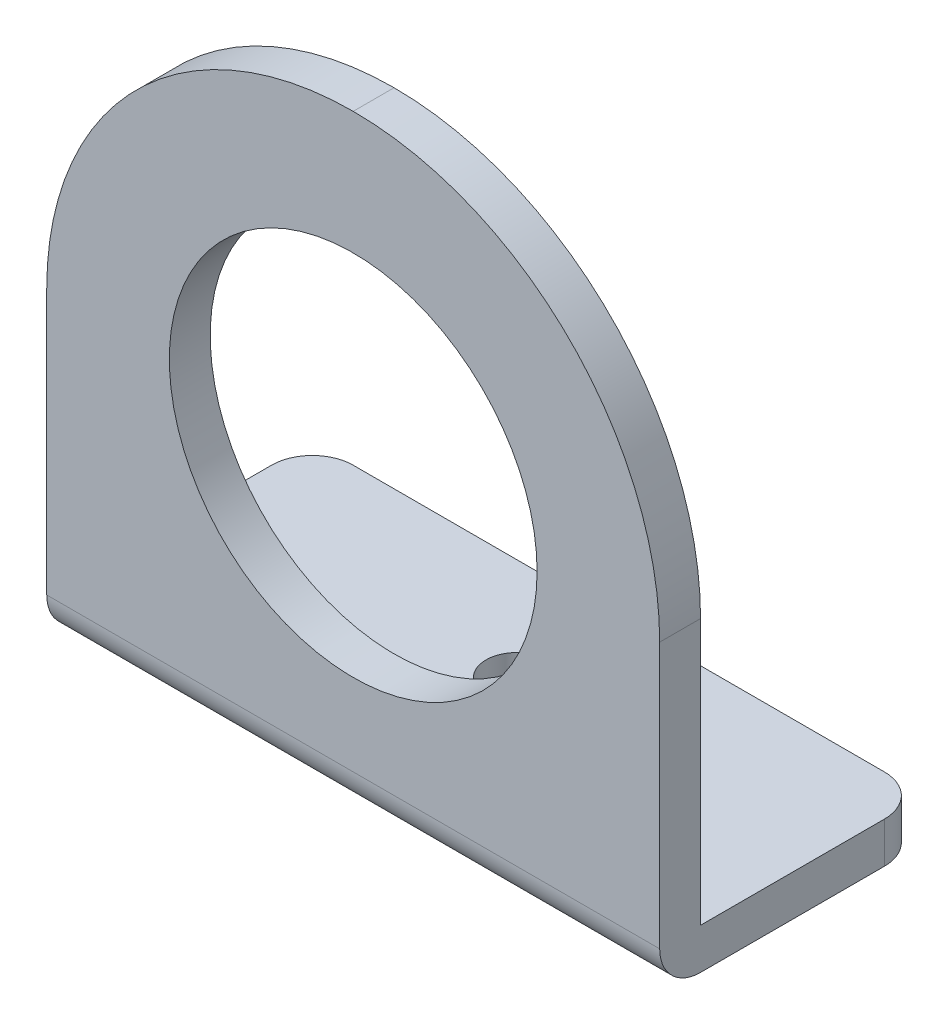
SolidWorks part; units mm, degrees
ref_plane "Front Plane" through (0, 0, 0) normal (0, 0, 1) x (1, 0, 0)
ref_plane "Top Plane" through (0, 0, 0) normal (0, 1, 0) x (1, 0, 0)
ref_plane "Right Plane" through (0, 0, 0) normal (1, 0, 0) x (0, 0, -1)
sketch "Sketch1" plane through (0, 0, 0) normal (0, 0, 1) x (1, 0, 0)
  line L1 (15, 15) -> (-15, 15)
  line L2 (15, 15) -> (15, -15)
  line L3 (15, -15) -> (-15, -15)
  line L4 (-15, 15) -> (-15, -15)
  line L5 (15, 15) -> (-15, -15) construction
  line L6 (15, -15) -> (-15, 15) construction
  point P0 (0, 0)
  dimension "D1" = 30
  dimension "D2" = 30
extrude "Boss-Extrude1" add sketch "Sketch1" along normal blind 2
sketch "Sketch2" plane through (0, 0, 2) normal (0, 0, 1) x (1, 0, 0)
  circle A0 centre (0, 0) radius 9
  dimension "D1" = 18
extrude "Cut-Extrude1" cut sketch "Sketch2" against normal through all contours A0
fillet "Fillet1" radius 15 2 edges at (-15, 15, 1) (15, 15, 1)
sketch "Sketch3" plane through (0, 0, 0) normal (0, 0, -1) x (-1, 0, 0)
  line L0 (15, 0) -> (15, -15) construction
  line L1 (-15, -15) -> (15, -15)
  line L2 (-15, -15) -> (-15, -13)
  line L3 (-15, -13) -> (15, -13)
  line L4 (15, -15) -> (15, -13)
  dimension "D1" = 2
extrude "Boss-Extrude2" add sketch "Sketch3" along normal blind 11
sketch "Sketch4" plane through (0, -13, 0) normal (0, 1, 0) x (1, 0, 0)
  line L0 (-15, 11) -> (15, 11) construction
  circle A0 centre (0, 6) radius 1.5
  dimension "D1" = 3
  dimension "D2" = 5
extrude "Cut-Extrude2" cut sketch "Sketch4" against normal through all
fillet "Fillet2" radius 2 3 edges at (0, -15, 2) (-15, -14, -11) (15, -14, -11)
